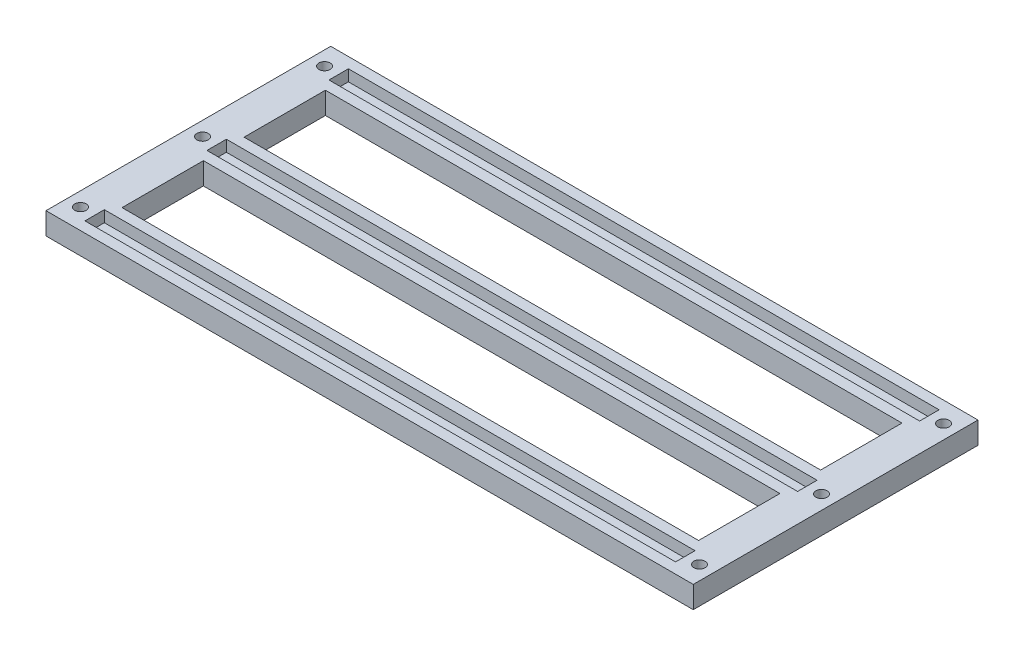
SolidWorks part; units mm, degrees
note: The reader was unsure of these and kept them because the rebuilt part matched: shared geometry of "Sketch1<3>".
ref_plane "Front Plane" through (0, 0, 0) normal (0, 0, 1) x (1, 0, 0)
ref_plane "Top Plane" through (0, 0, 0) normal (0, 1, 0) x (1, 0, 0)
ref_plane "Right Plane" through (0, 0, 0) normal (1, 0, 0) x (0, 0, -1)
sketch "Sketch1" plane through (0, 0, 0) normal (0, 1, 0) x (1, 0, 0)
  line L0 (-81.5, 28.75) -> (-81.5, 31.75)
  line L1 (-91.5, -40.25) -> (91.5, -40.25)
  line L2 (-91.5, -40.25) -> (-91.5, 40.25)
  line L3 (-91.5, 40.25) -> (91.5, 40.25)
  line L4 (91.5, -40.25) -> (91.5, 40.25)
  line L5 (0, 40.25) -> (0, -40.25) construction
  line L6 (-91.5, 0) -> (91.5, 0) construction
  line L7 (-81.5, 28.75) -> (81.5, 28.75)
  line L8 (-81.5, 28.75) -> (-81.5, 5.75)
  line L9 (-81.5, 5.75) -> (81.5, 5.75)
  line L10 (81.5, 28.75) -> (81.5, 5.75)
  line L11 (-81.5, -5.75) -> (81.5, -5.75)
  line L12 (-81.5, -5.75) -> (-81.5, -28.75)
  line L13 (-81.5, -28.75) -> (81.5, -28.75)
  line L14 (81.5, -5.75) -> (81.5, -28.75)
  line L15 (-81.5, 31.75) -> (-83.5, 31.75)
  line L16 (-83.5, 31.75) -> (-83.5, 37.25)
  line L17 (-83.5, 37.25) -> (-81.5, 37.25)
  line L18 (-81.5, 37.25) -> (-81.5, 40.25)
  line L19 (81.5, 28.75) -> (81.5, 31.75)
  line L20 (81.5, 31.75) -> (83.5, 31.75)
  line L21 (83.5, 31.75) -> (83.5, 37.25)
  line L22 (83.5, 37.25) -> (81.5, 37.25)
  line L23 (81.5, 37.25) -> (81.5, 40.25)
  line L24 (81.5, 2.75) -> (81.5, 5.75)
  line L25 (83.5, 2.75) -> (81.5, 2.75)
  line L26 (83.5, -2.75) -> (83.5, 2.75)
  line L27 (81.5, -2.75) -> (83.5, -2.75)
  line L28 (81.5, -5.75) -> (81.5, -2.75)
  line L29 (-81.5, 2.75) -> (-81.5, 5.75)
  line L30 (-83.5, 2.75) -> (-81.5, 2.75)
  line L31 (-83.5, -2.75) -> (-83.5, 2.75)
  line L32 (-81.5, -2.75) -> (-83.5, -2.75)
  line L33 (-81.5, -5.75) -> (-81.5, -2.75)
  line L34 (81.5, -31.75) -> (81.5, -28.75)
  line L35 (83.5, -31.75) -> (81.5, -31.75)
  line L36 (83.5, -37.25) -> (83.5, -31.75)
  line L37 (81.5, -37.25) -> (83.5, -37.25)
  line L38 (81.5, -40.25) -> (81.5, -37.25)
  line L39 (-81.5, -31.75) -> (-81.5, -28.75)
  line L40 (-83.5, -31.75) -> (-81.5, -31.75)
  line L41 (-83.5, -37.25) -> (-83.5, -31.75)
  line L42 (-81.5, -37.25) -> (-83.5, -37.25)
  line L43 (-81.5, -40.25) -> (-81.5, -37.25)
  line L44 (-81.5, 37.25) -> (81.5, 37.25)
  line L45 (-81.5, 31.75) -> (81.5, 31.75)
  line L46 (-81.5, 5.75) -> (81.5, 5.75)
  line L47 (81.5, -31.75) -> (-81.5, -31.75)
  line L48 (-81.5, -37.25) -> (81.5, -37.25)
  line L49 (-81.5, 2.75) -> (81.5, 2.75)
  line L50 (83.5, 37.25) -> (91.5, 37.25) construction
  line L51 (83.5, 31.75) -> (91.5, 31.75) construction
  line L52 (87.5, 37.25) -> (87.5, 31.75) construction
  line L53 (0, -55) -> (0, 55) construction
  line L54 (-81.5, -25.75) -> (81.5, -25.75) [skipped]
  line L55 (-81.5, -31.25) -> (81.5, -31.25) [skipped]
  line L56 (-81.5, 0.25) -> (81.5, 0.25) [skipped]
  line L57 (-81.5, -2.75) -> (81.5, -2.75)
  circle A0 centre (87.5, 34.5) radius 1.6
  circle A1 centre (-87.5, 34.5) radius 1.6
  circle A2 centre (-87.5, 0) radius 1.6
  circle A3 centre (87.5, 0) radius 1.6
  circle A4 centre (-87.5, -34.5) radius 1.6
  circle A5 centre (87.5, -34.5) radius 1.6
  point P0 (0, 0)
  dimension "D13" = 3.2
  dimension "D1" = 80.5
  dimension "D2" = 183
  dimension "D3" = 5.5
  dimension "D4" = 11.5
  dimension "D5" = 2
  dimension "D6" = 11.5
  dimension "D7" = 3
  dimension "D8" = 10
  dimension "D9" = 10
  dimension "D10" = 3
  dimension "D11" = 31.5
  dimension "D12" = 3
  dimension "D15" = 34.5
  dimension "D14" = 3
extrude "Boss-Extrude1" add sketch "Sketch1" along normal blind 3.2
extrude "Boss-Extrude2" add sketch "Sketch1<3>" against normal blind 3
sketch "Sketch1<3>" plane through (0, 0, 0) normal (0, 1, 0) x (1, 0, 0) same geometry as "Sketch1"
